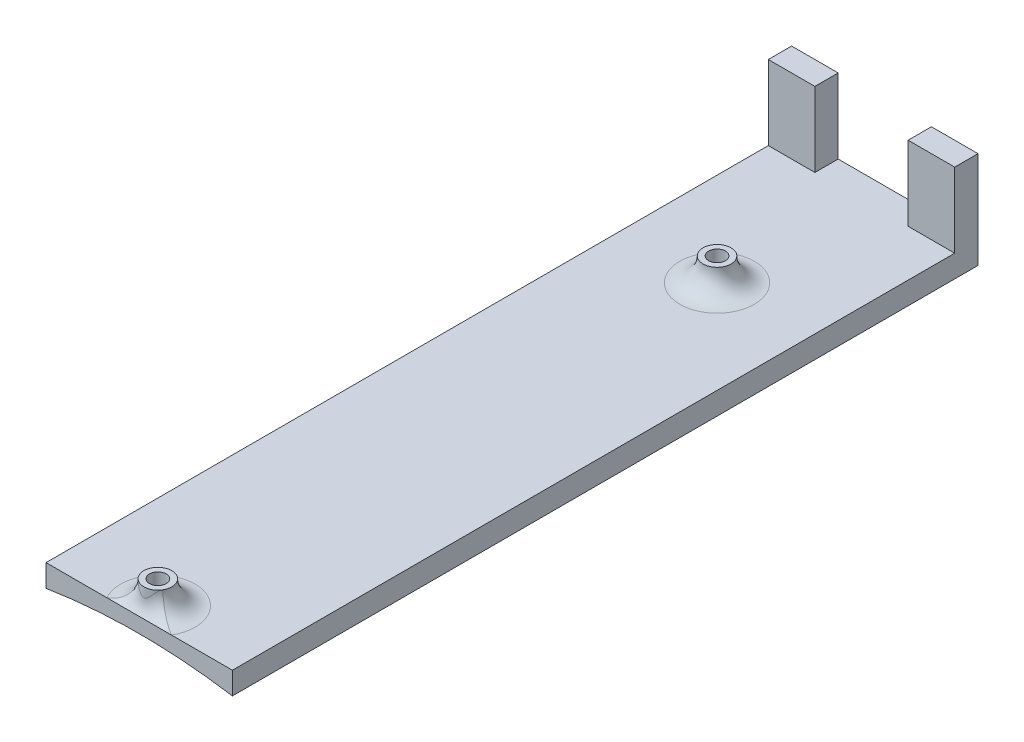
SolidWorks part; units mm, degrees
ref_plane "Front Plane" through (0, 0, 0) normal (0, 0, 1) x (1, 0, 0)
ref_plane "Top Plane" through (0, 0, 0) normal (0, 1, 0) x (1, 0, 0)
ref_plane "Right Plane" through (0, 0, 0) normal (1, 0, 0) x (0, 0, -1)
sketch "Sketch3" plane through (0, 0, 0) normal (0, 0, 1) x (1, 0, 0)
  line L0 (-12.7, -3.81) -> (12.7, -3.81)
  line L3 (-12.7, -6.8499) -> (-12.7, -3.81)
  line L4 (12.7, -6.8499) -> (12.7, -3.81)
  line L5 (0, -3.81) -> (0, -5.842) construction
  arc A2 (12.7, -6.8499) -> (-12.7, -6.8499) centre (0, -86.36) ccw
  circle A3 centre (0, 0) radius 15.24 construction
  point P7 (-12.5735, -4.0116)
  point P8 (0, 0)
  point P9 (0, -1.9538)
  point P10 (0, 0)
  dimension "D1" = 2.032
  dimension "D2" = 25.4
  dimension "D3" = 161.036
  dimension "D4" = 30.48
  dimension "D5" = 3.81
extrude "Boss-Extrude1" add sketch "Sketch3" along normal blind 101.6
sketch "Sketch4" plane through (0, -3.81, 0) normal (0, 1, 0) x (1, 0, 0)
  line L1 (12.7, -101.6) -> (-12.7, -101.6) construction
  circle A0 centre (0, -22.86) radius 1.143
  circle A1 centre (0, -99.06) radius 1.143
  circle A2 centre (0, -22.86) radius 1.905
  circle A3 centre (0, -99.06) radius 1.905
  dimension "D1" = 76.2
  dimension "D2" = 2.286
  dimension "D3" = 2.54
  dimension "D4" = 3.81
  dimension "D5" = 3.81
extrude "Boss-Extrude2" add sketch "Sketch4" along normal blind 3.175
fillet "Fillet1" radius 3.175 2 edges at (1.905, -3.81, 22.86) (1.905, -3.81, 99.06)
sketch "Sketch5" plane through (0, -3.81, 0) normal (0, 1, 0) x (1, 0, 0)
  line L0 (12.7, -101.6) -> (12.7, 0) construction
  line L1 (-12.7, 0) -> (12.7, 0)
  line L2 (-12.7, 0) -> (-12.7, -3.175)
  line L3 (-12.7, -3.175) -> (12.7, -3.175)
  line L4 (12.7, 0) -> (12.7, -3.175)
  dimension "D1" = 3.175
extrude "Boss-Extrude3" add sketch "Sketch5" along normal blind 10.16
sketch "Sketch8" plane through (0, 0, 0) normal (0, 0, -1) x (-1, 0, 0)
  line L0 (-12.7, 6.35) -> (12.7, 6.35) construction
  line L1 (6.35, -6.35) -> (-6.35, -6.35)
  line L2 (6.35, -6.35) -> (6.35, 6.35)
  line L3 (6.35, 6.35) -> (-6.35, 6.35)
  line L4 (-6.35, -6.35) -> (-6.35, 6.35)
  line L5 (6.35, -6.35) -> (-6.35, 6.35) construction
  line L6 (6.35, 6.35) -> (-6.35, -6.35) construction
  point P0 (0, 0)
  dimension "D1" = 12.7
extrude "Cut-Extrude1" cut sketch "Sketch8" against normal up to surface (3.175 mm away) up to face at (0, 1.27, 3.175)
sketch "Sketch9" plane through (0, 0, 3.175) normal (0, 0, -1) x (-1, 0, 0)
  line L3 (6.35, -3.81) -> (-6.35, -3.81)
  line L4 (-6.35, -3.81) -> (-6.35, -6.0928)
  line L5 (6.35, -6.0928) -> (6.35, -3.81)
  line L6 (6.35, -3.81) -> (-6.35, -3.81)
  line L7 (-6.35, -3.81) -> (-6.35, -6.0928)
  line L8 (6.35, -6.0928) -> (6.35, -3.81)
  arc A1 (6.35, -6.0928) -> (-6.35, -6.0928) centre (0, -86.36) ccw
  arc A2 (6.35, -6.0928) -> (-6.35, -6.0928) centre (0, -86.36) ccw
  dimension "D1" = 0
extrude "Boss-Extrude4" add sketch "Sketch9" along normal blind 3.175
